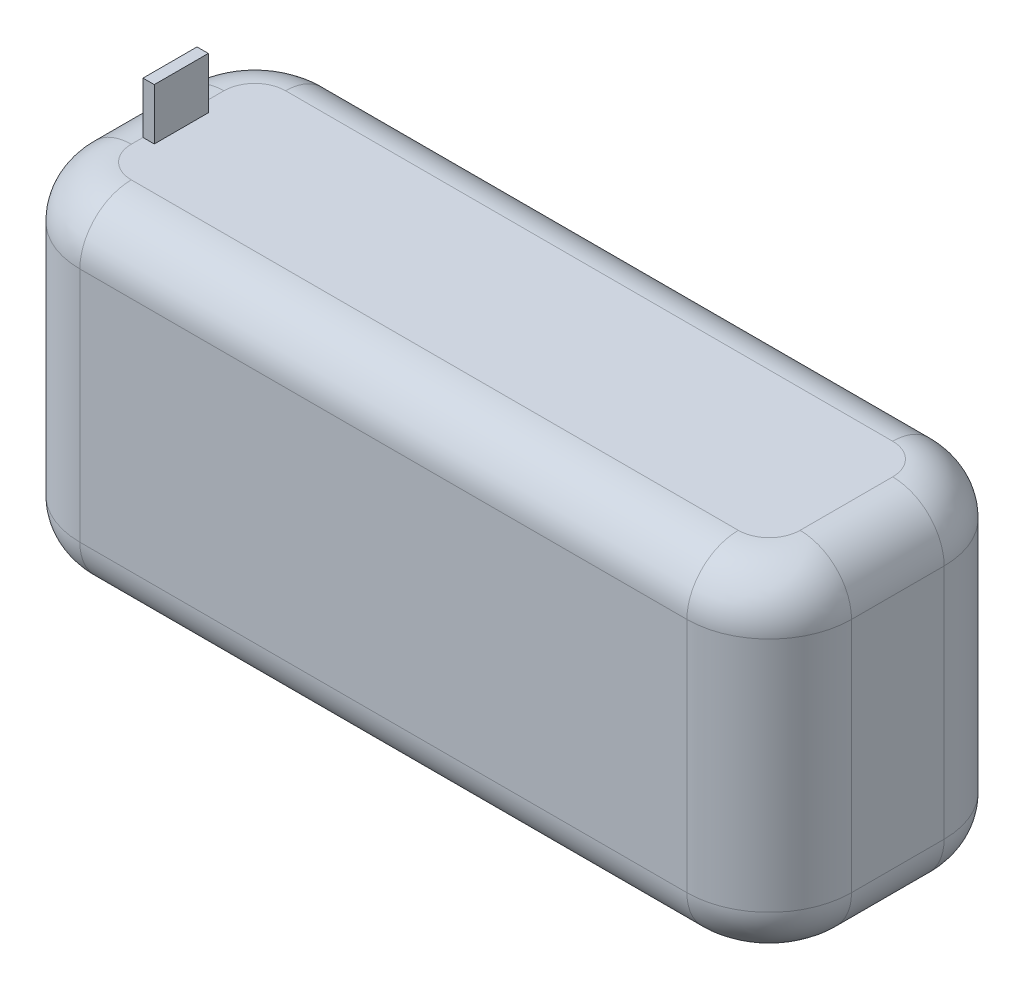
SolidWorks part; units mm, degrees
ref_plane "Front Plane" through (0, 0, 0) normal (0, 0, 1) x (1, 0, 0)
ref_plane "Top Plane" through (0, 0, 0) normal (0, 1, 0) x (1, 0, 0)
ref_plane "Right Plane" through (0, 0, 0) normal (1, 0, 0) x (0, 0, -1)
sketch "Sketch1" plane through (0, 0, 0) normal (0, 0, 1) x (1, 0, 0)
  line L1 (-37.5, -16.5) -> (37.5, -16.5)
  line L2 (-37.5, -16.5) -> (-37.5, 16.5)
  line L3 (-37.5, 16.5) -> (37.5, 16.5)
  line L4 (37.5, -16.5) -> (37.5, 16.5)
  line L5 (-37.5, -16.5) -> (37.5, 16.5) construction
  line L6 (-37.5, 16.5) -> (37.5, -16.5) construction
  point P0 (0, 0)
  dimension "D1" = 33
  dimension "D2" = 75
extrude "Boss-Extrude1" add sketch "Sketch1" along normal blind 25
fillet "Fillet1" radius 5 8 edges at (0, -16.5, 0) (0, -16.5, 25) (0, 16.5, 0) (0, 16.5, 25) (-37.5, 16.5, 12.5) (-37.5, -16.5, 12.5) (37.5, 16.5, 12.5) (37.5, -16.5, 12.5)
fillet "Fillet2" radius 8 12 edges at (-36.0355, -15.0355, 23.5355) (-36.0355, 15.0355, 23.5355) (-36.0355, -15.0355, 1.4645) (-36.0355, 15.0355, 1.4645) (36.0355, 15.0355, 1.4645) (36.0355, -15.0355, 1.4645) (36.0355, 15.0355, 23.5355) (36.0355, -15.0355, 23.5355) (37.5, 0, 25) (37.5, 0, 0) (-37.5, 0, 0) (-37.5, 0, 25)
sketch "Sketch2" plane through (0, -16.5, 0) normal (0, -1, 0) x (1, 0, 0)
  line L0 (-32.5, 17) -> (-32.5, 8) construction
  line L1 (-33.7767, 9.6838) -> (-31.2233, 9.6838)
  line L2 (-33.7767, 9.6838) -> (-33.7767, 15.3162)
  line L3 (-33.7767, 15.3162) -> (-31.2233, 15.3162)
  line L4 (-31.2233, 9.6838) -> (-31.2233, 15.3162)
  line L5 (-33.7767, 9.6838) -> (-31.2233, 15.3162) construction
  line L6 (-33.7767, 15.3162) -> (-31.2233, 9.6838) construction
  point P0 (-32.5, 12.5)
extrude "Boss-Extrude2" add sketch "Sketch2" along normal blind 5
sketch "Sketch3" plane through (0, 16.5, 0) normal (0, 1, 0) x (1, 0, 0)
  line L0 (-32.5, -8) -> (-32.5, -17) construction
  line L1 (-32.5, -10.6151) -> (-31.4034, -10.6151)
  line L2 (-32.5, -10.6151) -> (-32.5, -15.8667)
  line L3 (-32.5, -15.8667) -> (-31.4034, -15.8667)
  line L4 (-31.4034, -10.6151) -> (-31.4034, -15.8667)
extrude "Boss-Extrude3" add sketch "Sketch3" along normal blind 5
